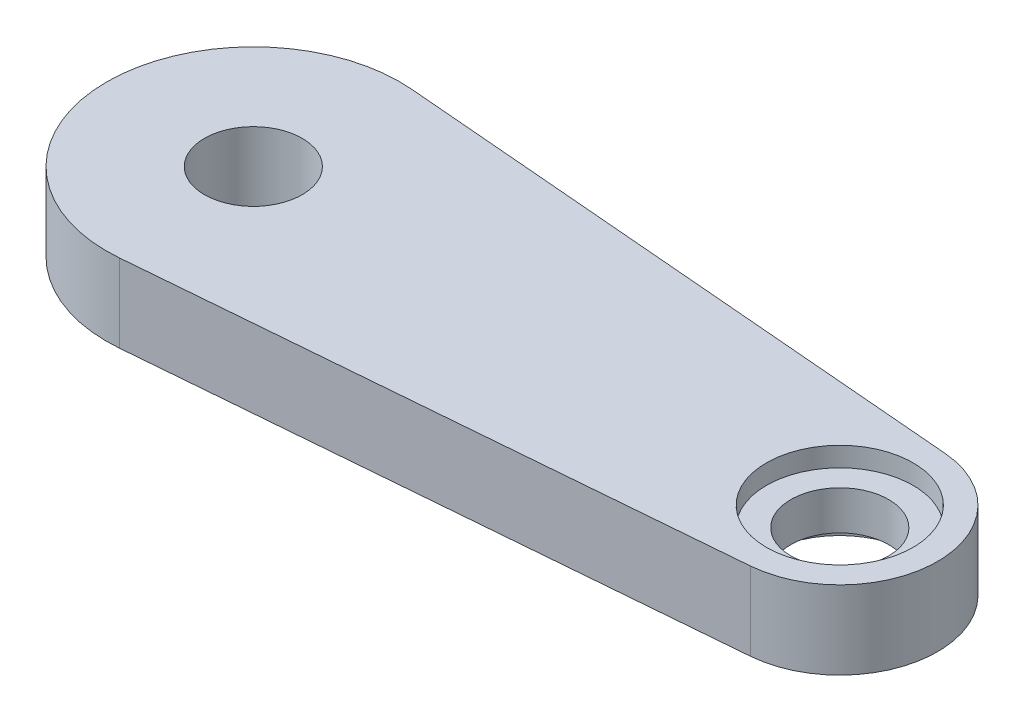
SolidWorks part; units mm, degrees
ref_plane "Front Plane" through (0, 0, 0) normal (0, 0, 1) x (1, 0, 0)
ref_plane "Top Plane" through (0, 0, 0) normal (0, 1, 0) x (1, 0, 0)
ref_plane "Right Plane" through (0, 0, 0) normal (1, 0, 0) x (0, 0, -1)
sketch "Sketch1" plane through (0, 0, 0) normal (0, 1, 0) x (1, 0, 0)
  line L0 (-71.875, 37.3696) -> (77.0833, 24.913)
  line L1 (-71.875, -37.3696) -> (77.0833, -24.913)
  arc A0 (-71.875, 37.3696) -> (-71.875, -37.3696) centre (-75, 0) ccw
  arc A1 (77.0833, -24.913) -> (77.0833, 24.913) centre (75, 0) ccw
  circle A2 centre (-75, 0) radius 12.5
  circle A3 centre (75, 0) radius 12.5
  circle A4 centre (75, 0) radius 18.75
  dimension "D3" = 75
  dimension "D4" = 50
  dimension "D5" = 25
  dimension "D6" = 25
  dimension "D7" = 37.5
  dimension "D1" = 75
  dimension "D2" = 75
extrude "Boss-Extrude1" add sketch "Sketch1" along normal mid plane 20 contours L1 A1 L0 A0 A4 A2 region at (-19.0683, 0, 0)
extrude "Boss-Extrude2" add sketch "Sketch1<3>" along normal mid plane 10 contours A4 A3 region at (56.7803, 0, 0)
sketch "Sketch1<3>" plane through (0, 0, 0) normal (0, 1, 0) x (1, 0, 0) same geometry as "Sketch1"
sketch "Sketch2" plane through (0, 10, 0) normal (0, 1, 0) x (1, 0, 0)
  line L0 (-7.9289, 20) -> (-15, 27.0711)
  line L5 (-5, 15) -> (5, 15)
  line L6 (-5, 15) -> (-5, 25)
  line L11 (-5, 25) -> (5, 25)
  line L12 (5, 15) -> (5, 25)
  line L17 (-5, 15) -> (5, 25) construction
  line L18 (-5, 25) -> (5, 15) construction
  line L23 (-7.9289, 20) -> (-15, 12.9289)
  line L24 (-15, 27.0711) -> (-22.0711, 20)
  line L29 (-15, 12.9289) -> (-22.0711, 20)
  line L30 (-7.9289, 20) -> (-22.0711, 20) construction
  line L31 (-15, 27.0711) -> (-15, 12.9289) construction
  line L32 (22.0711, 20) -> (15, 27.0711)
  line L33 (22.0711, 20) -> (15, 12.9289)
  line L34 (15, 27.0711) -> (7.9289, 20)
  line L35 (15, 12.9289) -> (7.9289, 20)
  line L36 (22.0711, 20) -> (7.9289, 20) construction
  line L37 (15, 27.0711) -> (15, 12.9289) construction
  point P0 (0, 20)
  point P6 (-15, 20)
  point P7 (15, 20)
  dimension "D1" = 10
  dimension "D2" = 15
  dimension "D3" = 15
  dimension "D4" = 15
surface "Surface-Plane1" sketch "Sketch2"
